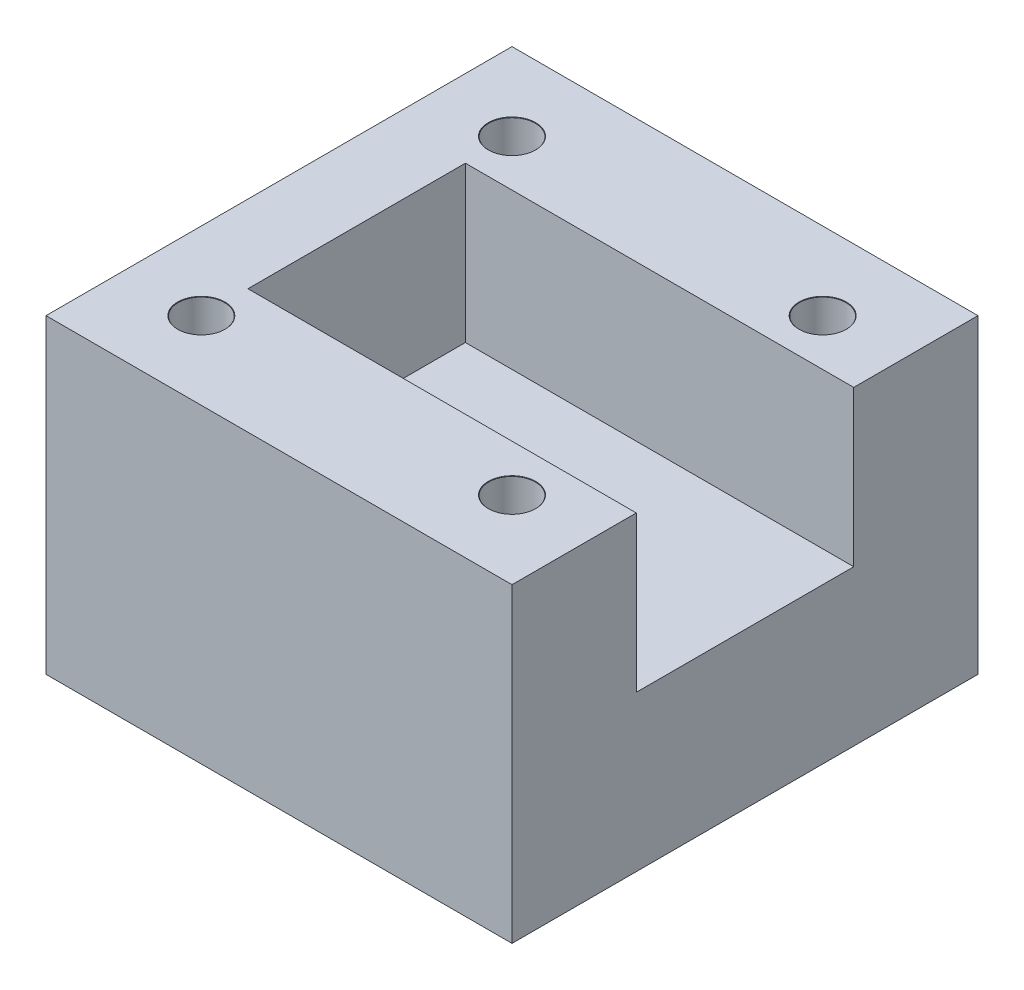
SolidWorks part; units mm, degrees
ref_plane "Front Plane" through (0, 0, 0) normal (0, 0, 1) x (1, 0, 0)
ref_plane "Top Plane" through (0, 0, 0) normal (0, 1, 0) x (1, 0, 0)
ref_plane "Right Plane" through (0, 0, 0) normal (1, 0, 0) x (0, 0, -1)
sketch "Sketch1" plane through (0, 23, 0) normal (0, 1, 0) x (1, 0, 0)
  line L0 (-288.3664, -197.9247) -> (-288.3664, -251.1066) construction
  line L5 (-273.3664, -205.9841) -> (-303.3664, -205.9841)
  line L6 (-273.3664, -205.9841) -> (-273.3664, -235.9841)
  line L7 (-273.3664, -235.9841) -> (-303.3664, -235.9841)
  line L8 (-303.3664, -205.9841) -> (-303.3664, -235.9841)
  line L9 (-273.3664, -220.9841) -> (-329.346, -220.9841) construction
  line L11 (-298.3664, -210.9841) -> (-278.3664, -210.9841) construction
  line L12 (-298.3664, -210.9841) -> (-298.3664, -230.9841) construction
  line L13 (-298.3664, -230.9841) -> (-278.3664, -230.9841) construction
  line L14 (-278.3664, -210.9841) -> (-278.3664, -230.9841) construction
  line L15 (-298.3664, -210.9841) -> (-278.3664, -230.9841) construction
  line L16 (-298.3664, -230.9841) -> (-278.3664, -210.9841) construction
  point P6 (-288.3664, -220.9841)
  point P14 (-288.3664, -235.9841)
  point P15 (-303.3664, -220.9841)
  point P17 (-302.3592, -214.2243)
  point P18 (-322.3592, -214.2243)
  point P19 (-322.3592, -234.2243)
  point P20 (-302.3592, -234.2243)
  point P23 (0, 0)
  dimension "D1" = 30
  dimension "D2" = 30
  dimension "D3" = 20
  dimension "D4" = 20
extrude "Boss-Extrude1" add sketch "Sketch1" along normal blind 20
sketch "Sketch2" plane through (0, 43, 0) normal (0, 1, 0) x (1, 0, 0)
  line L0 (-288.3664, -235.9841) -> (-288.3664, -181.7703) construction
  line L1 (-303.3664, -235.9841) -> (-273.3664, -235.9841) construction
  line L2 (-303.3664, -220.9841) -> (-253.0225, -220.9841) construction
  line L3 (-303.3664, -205.9841) -> (-303.3664, -235.9841) construction
  line L4 (-273.3664, -235.9841) -> (-273.3664, -205.9841) construction
  line L5 (-298.3664, -213.9841) -> (-273.3664, -213.9841)
  line L6 (-298.3664, -213.9841) -> (-298.3664, -227.9841)
  line L7 (-298.3664, -227.9841) -> (-273.3664, -227.9841)
  line L8 (-273.3664, -213.9841) -> (-273.3664, -227.9841)
  point P14 (-298.3664, -220.9841)
  point P15 (0, 0)
  dimension "D1" = 14
  dimension "D2" = 25
extrude "Cut-Extrude1" cut sketch "Sketch2" against normal blind 10
hole_wizard "Ø3.0mm Dowel Hole2" positions "Sketch8" profile "Sketch9" hole size "Ø3.0" standard "ANSI Metric" end condition through all
sketch "Sketch8" plane through (0, 43, 0) normal (0, 1, 0) x (1, 0, 0)
  point P0 (-298.3664, -210.9841)
  point P3 (-278.3664, -210.9841)
  point P6 (-278.3664, -230.9841)
  point P9 (-298.3664, -230.9841)
sketch "Sketch9" plane through (-298.3664, 43, 210.9841) normal (1, 0, 0) x (0, 0, 1)
  line L0 (0, 0) -> (0, 20)
  line L1 (0, 20) -> (1.5, 20)
  line L2 (1.5, 20) -> (1.5, 0.025)
  line L3 (1.5, 0.025) -> (1.525, 0)
  line L5 (1.525, 0) -> (0, 0)
  line L6 (-1.5, 0.025) -> (-1.525, 0) construction
  line L11 (0, -6.35) -> (0, 107.95) construction
  dimension "Thru Hole Dia." = 3
  dimension "Thru Hole Depth" = 20
  dimension "Near C'Sink Dia." = 3.05
  dimension "Near C'Sink Angle" = 90
